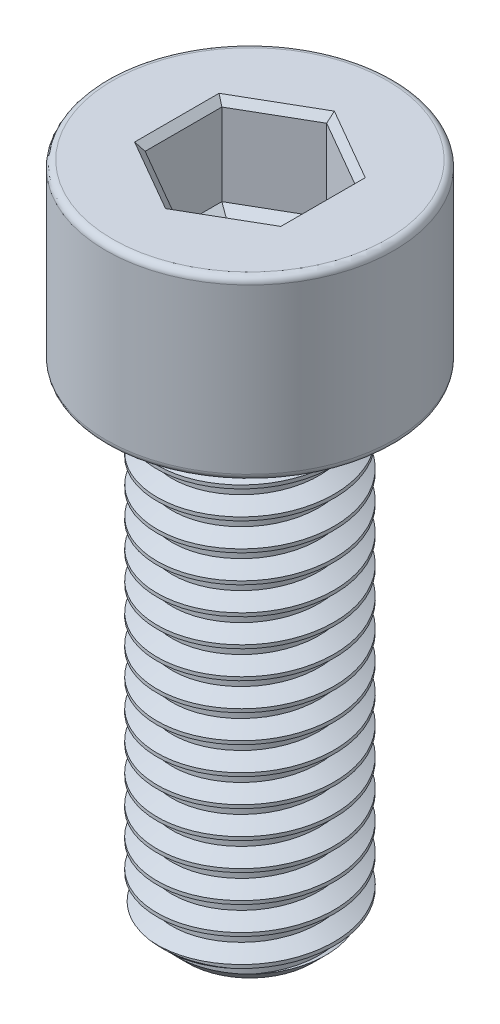
SolidWorks part; units mm, degrees
material "AISI Type A2 Tool Steel"
ref_plane "Front Plane" through (0, 0, 0) normal (0, 0, 1) x (1, 0, 0)
ref_plane "Top Plane" through (0, 0, 0) normal (0, 1, 0) x (1, 0, 0)
ref_plane "Right Plane" through (0, 0, 0) normal (1, 0, 0) x (0, 0, -1)
sketch "Sketch1" plane through (0, 0, 0) normal (0, 1, 0) x (1, 0, 0)
  circle A0 centre (0, 0) radius 4
  dimension "D1" = 8
extrude "Boss-Extrude1" add sketch "Sketch1" along normal blind 22
thread "Thread1" pitch 1.25 method cut profile "Thread Profile1" start angle 0, offset 1.25, length 0, pitch 1.25, diameter 8
ref_plane "Plane1" through (-4, 23.25, 0) normal (0, 0, 1) x (-1, 0, 0)
sketch "Thread Profile1" plane through (-4, 23.25, 0) normal (0, 0, 1) x (-1, 0, 0)
  line L0 (0, 0) -> (0, 1.25) construction
  line L11 (0, 0) -> (0, 1.0937)
  line L12 (0, 1.0937) -> (-0.6766, 0.7031)
  line L13 (-0.6766, 0.7031) -> (-0.6766, 0.3906)
  line L15 (-0.6766, 0.3906) -> (0, 0)
  line L17 (-0.6766, 0.5469) -> (0, 0.5469) construction
  point P2 (0, 0)
  dimension "Pitch" = 1.25
  dimension "Profile_Angle" = 60
  dimension "Profile_Land" = 0.3125
  dimension "Profile_Height" = 0.6766
sketch "Sketch2" plane through (0, 22, 0) normal (0, 1, 0) x (1, 0, 0)
  circle A0 centre (0, 0) radius 6.5
  dimension "D1" = 13
extrude "Boss-Extrude2" add sketch "Sketch2" along normal blind 8
sketch "Sketch5" plane through (0, 0, 0) normal (0, 0, 1) x (1, 0, 0)
  line L0 (0, 0) -> (0, 0.9986) construction
  line L1 (0, 0) -> (4.01, 0) construction
  line L2 (4.01, 0) -> (4.01, 1.2)
  line L3 (4.01, 1.2) -> (2.81, 0)
  line L4 (2.81, 0) -> (4.01, 0)
  dimension "D1" = 1.2
  dimension "D2" = 45
  dimension "D3" = 4.01
revolve "Cut-Revolve1" cut sketch "Sketch5" angle 360 about L0
fillet "Fillet1" radius 0.3 2 edges at (0, 30, 6.5) (0, 22, 6.5)
sketch "Sketch6" plane through (0, 30, 0) normal (0, 1, 0) x (1, 0, 0)
  line L1 (0, 3.4641) -> (-3, 1.7321)
  line L2 (-3, 1.7321) -> (-3, -1.7321)
  line L3 (-3, -1.7321) -> (0, -3.4641)
  line L4 (0, -3.4641) -> (3, -1.7321)
  line L5 (3, -1.7321) -> (3, 1.7321)
  line L6 (3, 1.7321) -> (0, 3.4641)
  circle A0 centre (0, 0) radius 3 construction
  dimension "D1" = 6
extrude "Cut-Extrude1" cut sketch "Sketch6" against normal blind 4
chamfer "Chamfer1" distance 0.3 angle 45 6 edges at (-3, 30, 0) (-1.5, 30, 2.5981) (1.5, 30, 2.5981) (3, 30, 0) (1.5, 30, -2.5981) (-1.5, 30, -2.5981)
sketch "Sketch7" plane through (0, 26, 0) normal (0, 1, 0) x (1, 0, 0)
  line L1 (0, 3.4641) -> (-3, 1.7321)
  line L2 (-3, 1.7321) -> (-3, -1.7321)
  line L3 (-3, -1.7321) -> (0, -3.4641)
  line L4 (0, -3.4641) -> (3, -1.7321)
  line L5 (3, -1.7321) -> (3, 1.7321)
  line L6 (3, 1.7321) -> (0, 3.4641)
  circle A0 centre (0, 0) radius 3 construction
extrude "Cut-Extrude2" cut sketch "Sketch7" against normal blind 0.4 draft 60
